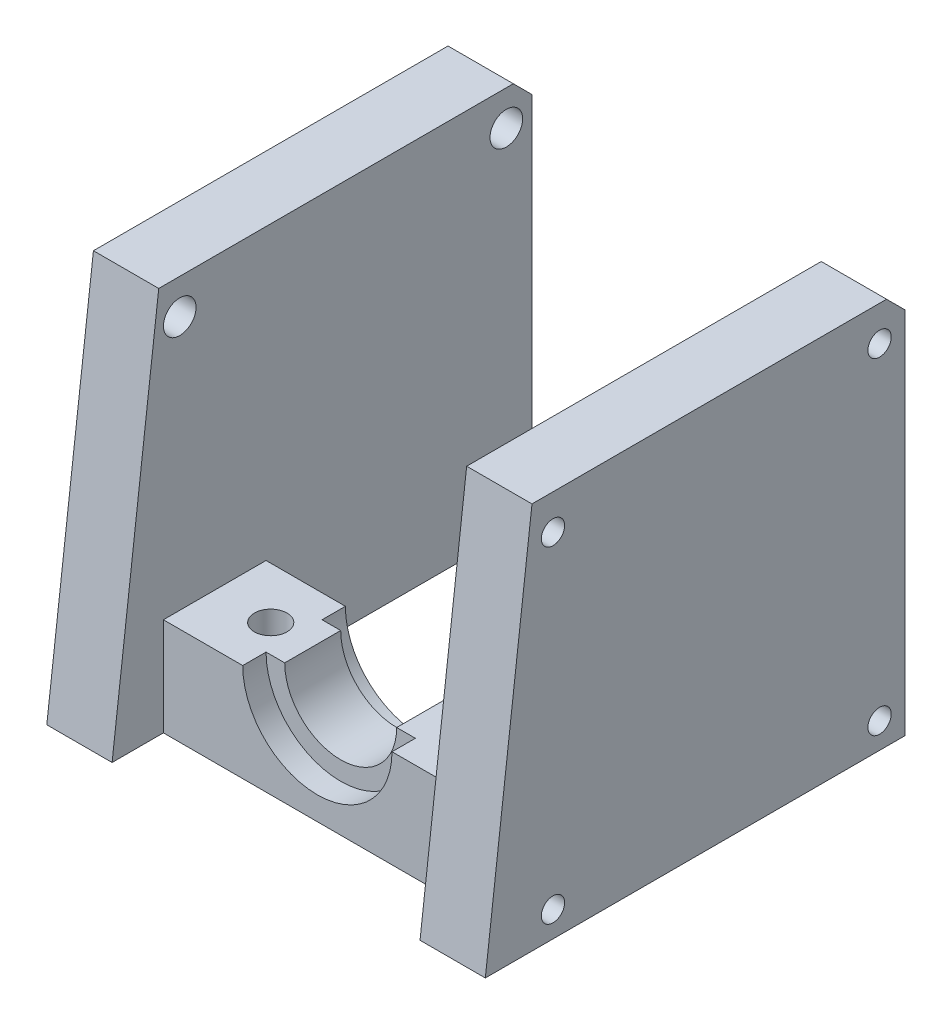
SolidWorks part; units mm, degrees
ref_plane "Front Plane" through (0, 0, 0) normal (0, 0, 1) x (1, 0, 0)
ref_plane "Top Plane" through (0, 0, 0) normal (0, 1, 0) x (1, 0, 0)
ref_plane "Right Plane" through (0, 0, 0) normal (1, 0, 0) x (0, 0, -1)
sketch "Sketch1" plane through (0, 0, 0) normal (0, 1, 0) x (1, 0, 0)
  line L0 (-16.5, 0) -> (16.5, 0) construction
  line L1 (-23.5, 45) -> (-16.5, 45)
  line L2 (-23.5, 45) -> (-23.5, 0)
  line L3 (-23.5, 0) -> (-16.5, 0)
  line L4 (-16.5, 45) -> (-16.5, 0)
  line L5 (0, 0) -> (0, 45) construction
  line L6 (16.5, 45) -> (16.5, 0)
  line L7 (23.5, 0) -> (16.5, 0)
  line L8 (23.5, 45) -> (23.5, 0)
  line L9 (23.5, 45) -> (16.5, 45)
  line L10 (-16.5, 5.5) -> (16.5, 5.5)
  line L11 (-16.5, 16.5) -> (16.5, 16.5)
  line L12 (-16.5, 11) -> (16.5, 11) construction
  circle A0 centre (-10.5, 11) radius 1.75
  circle A2 centre (10.5, 11) radius 1.75
  point P4 (0, 0)
  point P18 (0, 0)
  dimension "D6" = 3.5
  dimension "D1" = 7
  dimension "D2" = 45
  dimension "D3" = 33
  dimension "D4" = 5.5
  dimension "D5" = 11
  dimension "D7" = 21
extrude "Boss-Extrude1" add sketch "Sketch1" along normal blind 10.5 contours L11 L4 L10 L6 region at (0, 0, -11)
ref_plane "Plane1" through (0, 41.5, 0) normal (0, 1, 0) x (1, 0, 0)
sketch "Sketch2" plane through (0, 41.5, 0) normal (0, 1, 0) x (1, 0, 0)
  line L0 (-16.5, 45) -> (-16.5, 0) construction
  line L1 (-23.5, 45) -> (-16.5, 45)
  line L2 (-23.5, 45) -> (-23.5, 5)
  line L3 (-23.5, 5) -> (-16.5, 5)
  line L4 (-16.5, 45) -> (-16.5, 5)
  line L5 (0, 0) -> (0, 45) construction
  line L6 (0, 0) -> (0, 45) construction
  line L7 (16.5, 45) -> (16.5, 5)
  line L8 (23.5, 5) -> (16.5, 5)
  line L9 (23.5, 45) -> (23.5, 5)
  line L10 (23.5, 45) -> (16.5, 45)
  line L11 (-23.5, 45) -> (-23.5, 0) construction
  point P14 (-23.5, 45)
  dimension "D1" = 40
loft "Loft1" add section "Sketch2" section "Sketch1<3>" connector at (-23.5, 41.5, -5) connector at (-23.5, 0, 0)
sketch "Sketch1<3>" plane through (0, 0, 0) normal (0, 1, 0) x (1, 0, 0) same geometry as "Sketch1"
loft "Loft2" add section "Sketch2<3>" section "Sketch1<4>" connector at (23.5, 41.5, -5) connector at (23.5, 0, 0)
sketch "Sketch2<3>" plane through (0, 41.5, 0) normal (0, 1, 0) x (1, 0, 0) same geometry as "Sketch2"
sketch "Sketch1<4>" plane through (0, 0, 0) normal (0, 1, 0) x (1, 0, 0) same geometry as "Sketch1"
chamfer "Chamfer1" distance 2 2 edges
sketch "Sketch3" plane through (0, 0, 0) normal (1, 0, 0) x (0, 0, -1)
  line L0 (24.75, 0) -> (24.75, 41.5) construction
  line L1 (45, 0) -> (0, 0) construction
  line L2 (43, 41.5) -> (5, 41.5) construction
  line L3 (45, 20.25) -> (2.4398, 20.25) construction
  line L4 (45, 39.5) -> (45, 0) construction
  line L5 (5, 41.5) -> (0, 0) construction
  circle A0 centre (42.25, 2.75) radius 1.25
  circle A1 centre (42.25, 2.75) radius 1.75
  circle A2 centre (42.25, 37.75) radius 1.75
  circle A3 centre (42.25, 37.75) radius 1.25
  circle A4 centre (7.25, 37.75) radius 1.25
  circle A5 centre (7.25, 37.75) radius 1.75
  circle A6 centre (7.25, 2.75) radius 1.75
  circle A7 centre (7.25, 2.75) radius 1.25
  point P15 (35.5567, 36.1696)
  point P16 (42.175, 4.8217)
  dimension "D1" = 1.25
  dimension "D2" = 1.75
  dimension "D3" = 2.75
  dimension "D4" = 17.5
  dimension "D5" = 2.75
  dimension "D6" = 17.5
extrude "Cut-Extrude1" cut sketch "Sketch3" against normal through all both and the other way through all contours A4 | A3 | A0 region at (0, 2.75, -42.25) region at (0, 37.75, -42.25) region at (0, 37.75, -7.25)
extrude "Cut-Extrude2" cut sketch "Sketch3<3>" against normal blind 20.5 and the other way blind 20.5 contours A5 A4 | A2 A3 | A1 A0 region at (0, 2.75, -40.5495) region at (0, 37.75, -40.5495) region at (0, 37.75, -5.5495)
sketch "Sketch3<3>" plane through (0, 0, 0) normal (1, 0, 0) x (0, 0, -1) same geometry as "Sketch3"
extrude "Cut-Extrude3" cut sketch "Sketch3<6>" against normal blind 8 from surface contours A7 region at (0, 2.75, -7.25) starting at face at (23.5, 37.75, -6)
sketch "Sketch3<6>" plane through (0, 0, 0) normal (1, 0, 0) x (0, 0, -1) same geometry as "Sketch3"
extrude "Cut-Extrude4" cut sketch "Sketch3<7>" along normal blind 8 from surface contours A7 region at (0, 2.75, -7.25) starting at face at (-23.5, 37.75, -8.5)
sketch "Sketch3<7>" plane through (0, 0, 0) normal (1, 0, 0) x (0, 0, -1) same geometry as "Sketch3"
ref_plane "Plane2" through (0, 0, -11) normal (0, 0, 1) x (1, 0, 0)
sketch "Sketch4" plane through (0, 0, -11) normal (0, 0, 1) x (1, 0, 0)
  line L0 (-16.5, 10.5) -> (16.5, 10.5) construction
  line L1 (-8, 10.5) -> (8, 10.5)
  circle A0 centre (0, 10.5) radius 6
  circle A1 centre (0, 10.5) radius 8
  dimension "D1" = 8
  dimension "D2" = 6
extrude "Cut-Extrude5" cut sketch "Sketch4" against normal through all both and the other way through all contours L1 A1 A0 | L1 A0 region at (0, 7.9535, -11) region at (7, 10.3211, -11)
extrude "Boss-Extrude2" add sketch "Sketch4<4>" along normal mid plane 6 contours L1 A1 A0 region at (7, 10.3211, -11)
sketch "Sketch4<4>" plane through (0, 0, -11) normal (0, 0, 1) x (1, 0, 0) same geometry as "Sketch4"
